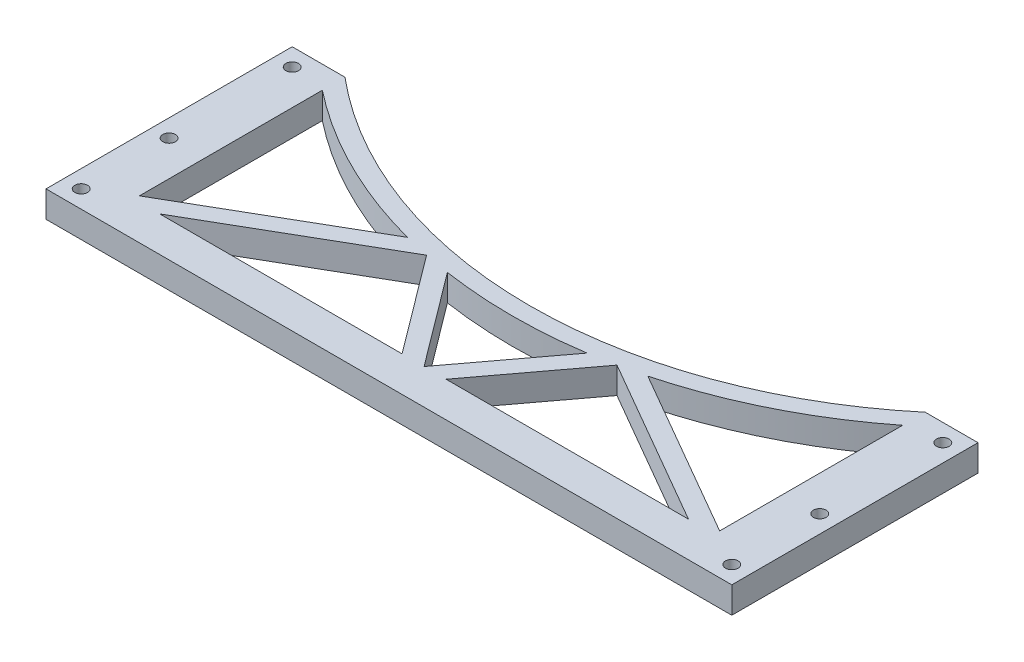
SolidWorks part; units mm, degrees
ref_plane "Front Plane" through (0, 0, 0) normal (0, 0, 1) x (1, 0, 0)
ref_plane "Top Plane" through (0, 0, 0) normal (0, 1, 0) x (1, 0, 0)
ref_plane "Right Plane" through (0, 0, 0) normal (1, 0, 0) x (0, 0, -1)
sketch "Sketch1" plane through (0, 0, 0) normal (0, 1, 0) x (1, 0, 0)
  line L0 (-123.825, 88.9) -> (-104.775, 88.9)
  line L1 (-123.825, 0) -> (123.825, 0)
  line L2 (-123.825, 0) -> (-123.825, 88.9)
  line L4 (123.825, 0) -> (123.825, 88.9)
  line L5 (123.825, 88.9) -> (104.775, 88.9)
  arc A1 (-104.775, 88.9) -> (104.775, 88.9) centre (0, 213.9156) ccw
  point P4 (0, 0)
  point P9 (0, 50.8)
  dimension "D3" = 247.65
  dimension "D4" = 50.8
  dimension "D1" = 19.05
  dimension "D2" = 88.9
extrude "Boss-Extrude1" add sketch "Sketch1" along normal blind 9.525
sketch "Sketch2" plane through (0, 9.525, 0) normal (0, 1, 0) x (1, 0, 0)
  line L0 (-104.775, 80.721) -> (-104.775, 14.6647)
  line L1 (-104.775, 14.6647) -> (-43.3976, 50.101)
  line L2 (-95.478, 12.7) -> (-7.9363, 12.7)
  line L3 (-95.478, 12.7) -> (-34.3811, 47.9743)
  line L4 (-123.825, 0) -> (-97.0655, 15.4496) construction
  line L5 (-98.653, 18.1993) -> (-95.478, 12.7) construction
  line L6 (0, 12.7) -> (-25.2172, 46.3367)
  line L7 (0, 44.45) -> (0, 12.7)
  line L8 (-34.3811, 47.9743) -> (-7.9363, 12.7)
  line L9 (-123.825, 88.9) -> (-123.825, 0) construction
  line L10 (-123.825, 0) -> (123.825, 0) construction
  arc A0 (-104.775, 88.9) -> (104.775, 88.9) centre (0, 213.9156) ccw construction
  arc A1 (-104.775, 80.721) -> (-43.3976, 50.101) centre (0, 213.9156) ccw
  arc A2 (-25.2172, 46.3367) -> (0, 44.45) centre (0, 213.9156) ccw
  point P12 (-97.0655, 15.4496)
  dimension "D5" = 6.35
  dimension "D1" = 6.35
  dimension "D2" = 19.05
  dimension "D3" = 6.35
  dimension "D4" = 12.7
  dimension "D6" = 30
extrude "Cut-Extrude1" cut sketch "Sketch2" against normal through all
mirror "Mirror1" about plane through (0, 0, 0) normal (1, 0, 0) of "Cut-Extrude1"
sketch "Sketch3" plane through (0, 9.525, 0) normal (0, 1, 0) x (1, 0, 0)
  line L0 (-104.775, 88.9) -> (-123.825, 88.9) construction
  line L1 (-123.825, 88.9) -> (-123.825, 0) construction
  line L2 (-123.825, 0) -> (123.825, 0) construction
  line L3 (123.825, 88.9) -> (104.775, 88.9) construction
  line L4 (123.825, 0) -> (123.825, 88.9) construction
  circle A0 centre (117.475, 82.55) radius 2.286
  circle A1 centre (117.475, 6.35) radius 2.286
  circle A2 centre (-117.475, 82.55) radius 2.286
  circle A3 centre (-117.475, 6.35) radius 2.286
  circle A4 centre (117.475, 38.1) radius 2.286
  circle A5 centre (-117.475, 38.1) radius 2.286
  point P8 (0, 0)
  point P23 (0, 0)
  dimension "D1" = 4.572
  dimension "D2" = 6.35
  dimension "D3" = 6.35
  dimension "D4" = 6.35
  dimension "D5" = 6.35
  dimension "D6" = 6.35
  dimension "D7" = 6.35
  dimension "D8" = 31.75
extrude "Cut-Extrude2" cut sketch "Sketch3" against normal through all
